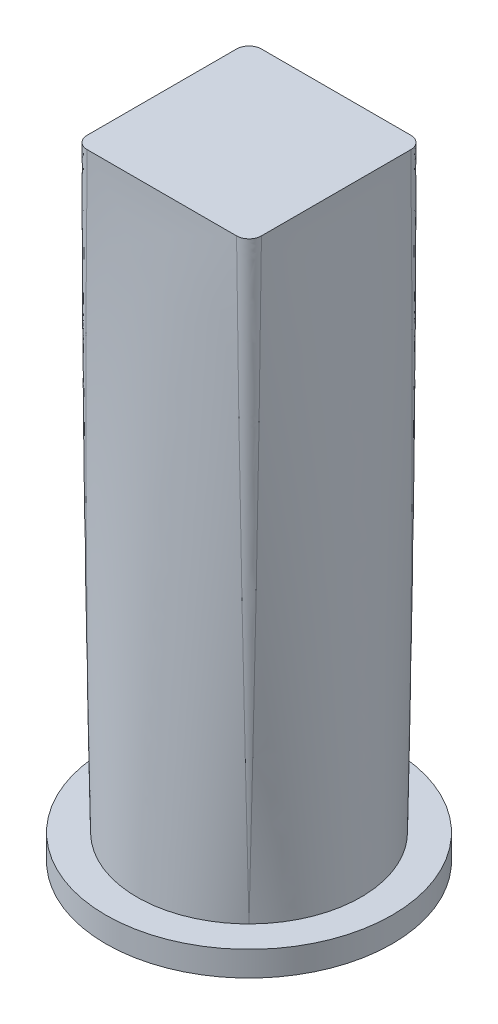
SolidWorks part; units mm, degrees
ref_plane "Front Plane" through (0, 0, 0) normal (0, 0, 1) x (1, 0, 0)
ref_plane "Top Plane" through (0, 0, 0) normal (0, 1, 0) x (1, 0, 0)
ref_plane "Right Plane" through (0, 0, 0) normal (1, 0, 0) x (0, 0, -1)
sketch "Sketch1" plane through (0, 0, 0) normal (0, 1, 0) x (1, 0, 0)
  line L0 (-10.5349, 52.9624) -> (0, 0) construction
  line L1 (0, 0) -> (21.9027, 0) construction
  circle A2 centre (0, 0) radius 57.5
  circle A3 centre (0, 0) radius 54 construction
  point P41 (0, 0)
  dimension "D2" = 108
  dimension "D3" = 115
  dimension "D4" = 101.25
extrude "Boss-Extrude1" add sketch "Sketch1" along normal blind 10
sketch "Sketch4" plane through (0, 10, 0) normal (0, 1, 0) x (1, 0, 0)
  line L1 (35, -35) -> (35, 35) construction
  line L2 (35, 35) -> (-35, 35) construction
  line L3 (-35, 35) -> (-35, -35) construction
  line L4 (-35, -35) -> (35, -35) construction
  circle A1 centre (0, 0) radius 35 construction
  circle A2 centre (0, 0) radius 45
  dimension "D1" = 70
  dimension "D2" = 90
ref_plane "Plane2" through (0, 250, 0) normal (0, 1, 0) x (1, 0, 0)
sketch "Sketch9" plane through (0, 250, 0) normal (0, 1, 0) x (1, 0, 0)
  line L1 (35, -35) -> (35, 35)
  line L2 (35, 35) -> (-35, 35)
  line L3 (-35, 35) -> (-35, -35)
  line L4 (-35, -35) -> (35, -35)
  circle A0 centre (0, 0) radius 35 construction
loft "Loft1" add profiles "Sketch9", "Sketch4" connector at (-35, 250, -35) connector at (-0.4241, 10, -44.998)
fillet "Fillet2" radius 5 4 edges
